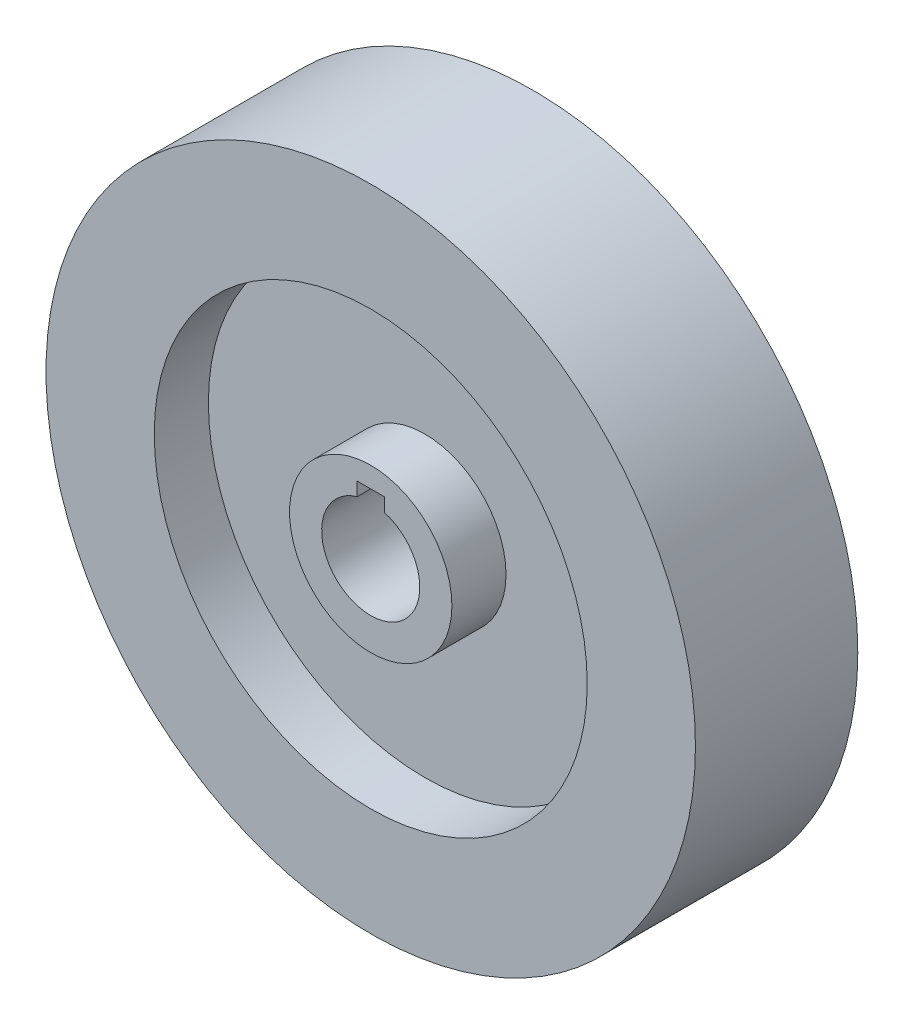
SolidWorks part; units mm, degrees
ref_plane "Front Plane" through (0, 0, 0) normal (0, 0, 1) x (1, 0, 0)
ref_plane "Top Plane" through (0, 0, 0) normal (0, 1, 0) x (1, 0, 0)
ref_plane "Right Plane" through (0, 0, 0) normal (1, 0, 0) x (0, 0, -1)
sketch "Sketch1" plane through (0, 0, 0) normal (1, 0, 0) x (0, 0, -1)
  line L0 (-34.2145, 0) -> (34.2145, 0) construction
  line L1 (0, 0) -> (0, 76.2) construction
  line L2 (19.05, 11.5094) -> (-19.05, 11.5094)
  line L3 (-19.05, 11.5094) -> (-19.05, 19.05)
  line L4 (-19.05, 19.05) -> (-6.35, 19.05)
  line L5 (-6.35, 19.05) -> (-6.35, 50.8)
  line L6 (-6.35, 50.8) -> (-19.05, 50.8)
  line L7 (-19.05, 50.8) -> (-19.05, 76.2)
  line L8 (-19.05, 76.2) -> (19.05, 76.2)
  line L9 (19.05, 11.5094) -> (19.05, 19.05)
  line L10 (19.05, 19.05) -> (6.35, 19.05)
  line L11 (6.35, 19.05) -> (6.35, 50.8)
  line L12 (6.35, 50.8) -> (19.05, 50.8)
  line L13 (19.05, 50.8) -> (19.05, 76.2)
  point P13 (0, 11.5094)
  dimension "D1" = 38.1
  dimension "D2" = 152.4
  dimension "D3" = 23.0188
  dimension "D4" = 12.7
  dimension "D5" = 38.1
  dimension "D6" = 25.4
revolve "Revolve1" add sketch "Sketch1" angle 360 about L0
sketch "Sketch4" plane through (0, 0, -19.05) normal (0, 0, -1) x (-1, 0, 0)
  line L0 (-3.175, 11.0628) -> (3.175, 11.0628)
  line L1 (3.175, 11.0628) -> (3.175, 14.2378)
  line L2 (3.175, 14.2378) -> (-3.175, 14.2378)
  line L3 (-3.175, 14.2378) -> (-3.175, 11.0628)
  circle A0 centre (0, 0) radius 11.5094 construction
  dimension "D1" = 6.35
  dimension "D2" = 3.175
extrude "Cut-Extrude1" cut sketch "Sketch4" against normal through all
